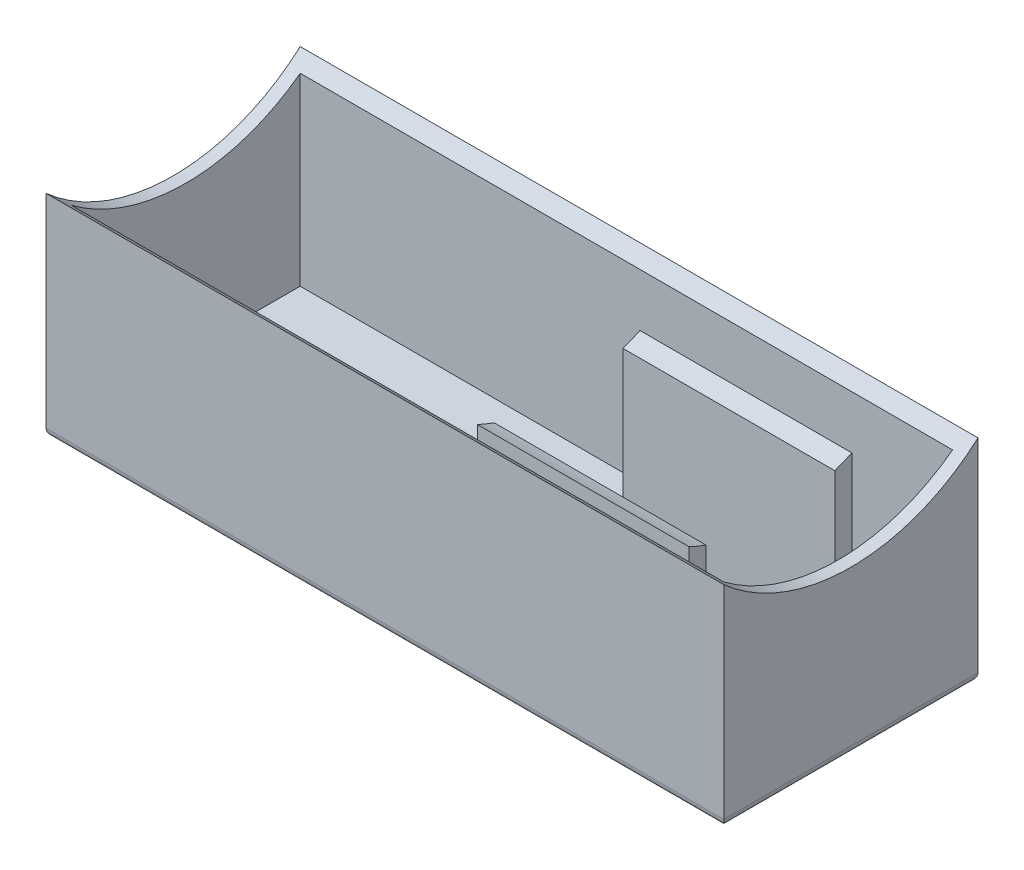
SolidWorks part; units mm, degrees
material "Thornel Mat VMA"
ref_plane "Front Plane" through (0, 0, 0) normal (0, 0, 1) x (1, 0, 0)
ref_plane "Top Plane" through (0, 0, 0) normal (0, 1, 0) x (1, 0, 0)
ref_plane "Right Plane" through (0, 0, 0) normal (1, 0, 0) x (0, 0, -1)
sketch "Sketch1" plane through (0, 0, 0) normal (0, 1, 0) x (1, 0, 0)
  line L0 (-38.5, -13.5) -> (-38.5, 13.5)
  line L1 (-40, -15) -> (40, -15)
  line L2 (-40, -15) -> (-40, 15)
  line L3 (-40, 15) -> (40, 15)
  line L4 (40, -15) -> (40, 15)
  line L5 (-40, -15) -> (40, 15) construction
  line L6 (-40, 15) -> (40, -15) construction
  line L7 (-38.5, 13.5) -> (38.5, 13.5)
  line L8 (38.5, -13.5) -> (38.5, 13.5)
  line L9 (-38.5, -13.5) -> (38.5, -13.5)
  point P0 (0, 0)
  dimension "D1" = 80
  dimension "D2" = 30
  dimension "D3" = 1.5
extrude "Boss-Extrude1" add sketch "Sketch1" along normal blind 2 contours L0 L9 L8 L7 | L1 L4 L3 L2 L9 L0 L7 L8 | L0 L7 L8 L9 | L2 L1 L4 L3 region at (0, 0, 0) region at (-39.1456, 0, 0)
extrude "Boss-Extrude2" add sketch "Sketch1<3>" along normal blind 25
sketch "Sketch1<3>" plane through (0, 0, 0) normal (0, 1, 0) x (1, 0, 0) same geometry as "Sketch1"
sketch "Sketch2" plane through (0, 2, 0) normal (0, 1, 0) x (1, 0, 0)
  line L0 (38.5, 13.5) -> (38.5, -13.5) construction
  line L1 (5.5, -7.6) -> (30.5, -7.6)
  line L2 (5.5, -7.6) -> (5.5, 7.6)
  line L3 (5.5, 7.6) -> (30.5, 7.6)
  line L4 (30.5, -7.6) -> (30.5, 7.6)
  line L5 (5.5, -7.6) -> (30.5, 7.6) construction
  line L6 (5.5, 7.6) -> (30.5, -7.6) construction
  line L7 (3.5, -9.6) -> (3.5, 9.6)
  line L8 (3.5, 9.6) -> (32.5, 9.6)
  line L9 (32.5, -9.6) -> (32.5, 9.6)
  line L10 (3.5, -9.6) -> (32.5, -9.6)
  line L11 (5.5, 9.6) -> (5.5, -9.6)
  line L12 (30.5, 9.6) -> (30.5, -9.6)
  point P0 (18, 0)
  dimension "D1" = 15.2
  dimension "D2" = 25
  dimension "D3" = 8
  dimension "D4" = 2
extrude "Boss-Extrude3" add sketch "Sketch2" along normal up to surface (23 mm away) contours L12 L8 L11 L3 | L12 L1 L11 L10 region at (18, 2, 8.6) region at (18, 2, -8.6) up to face at (0, 25, 0)
sketch "Sketch3" plane through (40, 0, 0) normal (1, 0, 0) x (0, 0, -1)
  line L0 (-15, 25) -> (15, 25) construction
  line L1 (-15, 25) -> (15, 25)
  arc A0 (-15, 25) -> (15, 25) centre (0, 41.7705) ccw
  dimension "D1" = 22.5
extrude "Cut-Extrude1" cut sketch "Sketch3" against normal through all
fillet "Fillet1" radius 1 4 edges at (40, 0, 0) (0, 0, -15) (-40, 0, 0) (0, 0, 15)
